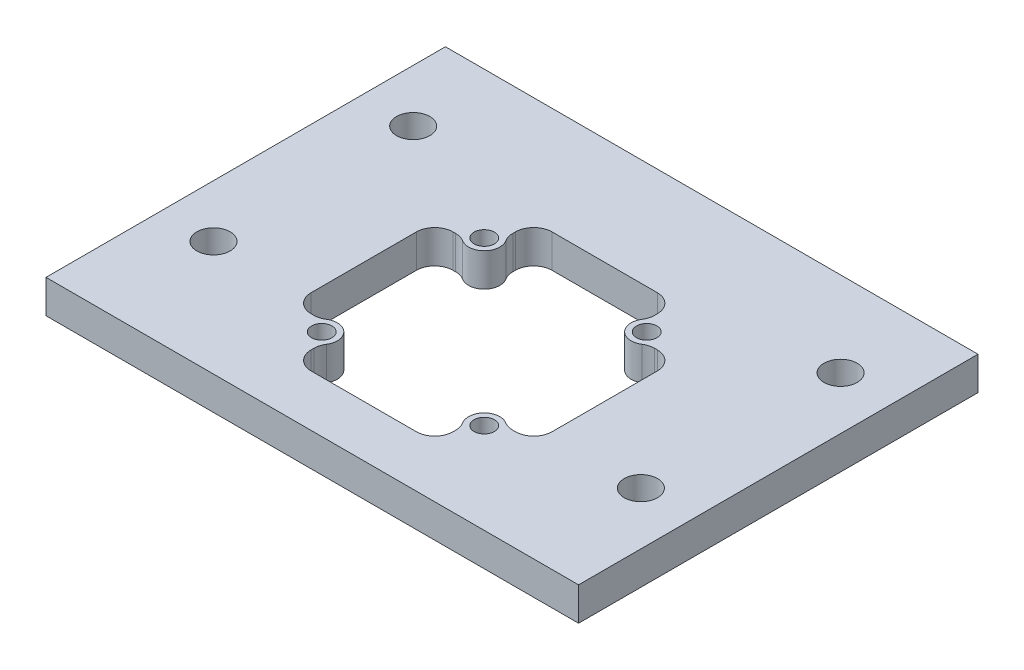
SolidWorks part; units mm, degrees
ref_plane "Front Plane" through (0, 0, 0) normal (0, 0, 1) x (1, 0, 0)
ref_plane "Top Plane" through (0, 0, 0) normal (0, 1, 0) x (1, 0, 0)
ref_plane "Right Plane" through (0, 0, 0) normal (1, 0, 0) x (0, 0, -1)
sketch "Sketch1" plane through (0, 0, 0) normal (0, 1, 0) x (1, 0, 0)
  line L1 (-50.8, 38.1) -> (50.8, 38.1)
  line L2 (-50.8, 38.1) -> (-50.8, -38.1)
  line L3 (-50.8, -38.1) -> (50.8, -38.1)
  line L4 (50.8, 38.1) -> (50.8, -38.1)
  line L5 (-50.8, 38.1) -> (50.8, -38.1) construction
  line L6 (-50.8, -38.1) -> (50.8, 38.1) construction
  point P0 (0, 0)
  dimension "D1" = 101.6
  dimension "D2" = 76.2
extrude "Boss-Extrude1" add sketch "Sketch1" along normal mid plane 6.35
sketch "Sketch16" plane through (0, 3.175, 0) normal (0, 1, 0) x (1, 0, 0)
  line L0 (50.8, 38.1) -> (-50.8, 38.1) construction
  line L1 (-50.8, 38.1) -> (-50.8, -38.1) construction
  line L2 (0, -55) -> (0, 55) construction
  point P0 (-30, 12.7)
  point P10 (30, 12.7)
  dimension "D1" = 25.4
  dimension "D2" = 20.8
sketch "Sketch25" plane through (0, 3.175, 0) normal (0, 1, 0) x (1, 0, 0)
  point P0 (-40.767, 21.9177)
  point P1 (-40.767, -16.1823)
  dimension "D1" = 40.767
  dimension "D2" = 38.1
hole_wizard "1/4 (0.25) Diameter Hole1" positions "Sketch26" profile "Sketch27" hole size "1/4" standard "ANSI Inch" end condition through all
sketch "Sketch26" plane through (0, 3.175, 0) normal (0, 1, 0) x (1, 0, 0)
  point P0 (-40.767, 21.9177)
  point P3 (-40.767, -16.1823)
sketch "Sketch27" plane through (-40.767, 3.175, -21.9177) normal (1, 0, 0) x (0, 0, 1)
  line L0 (0, 0) -> (0, 6.35)
  line L1 (0, 6.35) -> (3.175, 6.35)
  line L2 (3.175, 6.35) -> (3.175, 0)
  line L5 (3.175, 0) -> (0, 0)
  line L11 (0, -6.35) -> (0, 107.95) construction
  dimension "Thru Hole Dia." = 6.35
  dimension "Thru Hole Depth" = 6.35
sketch "Sketch17" plane through (0, 3.175, 0) normal (0, 1, 0) x (1, 0, 0)
  line L0 (-30, 12.7) -> (30, 12.7) construction
  line L1 (-21, -26.3) -> (21, -26.3) construction
  line L2 (-21, -26.3) -> (-21, 15.7) construction
  line L3 (-21, 15.7) -> (21, 15.7) construction
  line L4 (21, -26.3) -> (21, 15.7) construction
  line L5 (-21, -26.3) -> (21, 15.7) construction
  line L6 (-21, 15.7) -> (21, -26.3) construction
  line L7 (-15.5, -20.8) -> (15.5, -20.8) construction
  line L8 (-15.5, -20.8) -> (-15.5, 10.2) construction
  line L9 (-15.5, 10.2) -> (15.5, 10.2) construction
  line L10 (15.5, -20.8) -> (15.5, 10.2) construction
  line L11 (-15.5, -20.8) -> (15.5, 10.2) construction
  line L12 (-15.5, 10.2) -> (15.5, -20.8) construction
  point P0 (0, -5.3)
  point P5 (0, -5.3)
  point P10 (0, 12.7)
  dimension "D1" = 31
  dimension "D2" = 42
  dimension "D3" = 18
hole_wizard "M3.5 Clearance Hole1" positions "Sketch19" profile "Sketch20" hole size "M3.5" standard "ANSI Metric" end condition through all
sketch "Sketch19" plane through (0, 3.175, 0) normal (0, 1, 0) x (1, 0, 0)
  point P0 (-15.5, 10.2)
  point P3 (15.5, 10.2)
  point P6 (15.5, -20.8)
  point P9 (-15.5, -20.8)
sketch "Sketch20" plane through (-15.5, 3.175, -10.2) normal (1, 0, 0) x (0, 0, 1)
  line L0 (0, 0) -> (0, 6.35)
  line L1 (0, 6.35) -> (1.95, 6.35)
  line L2 (1.95, 6.35) -> (1.95, 0)
  line L5 (1.95, 0) -> (0, 0)
  line L11 (0, -6.35) -> (0, 107.95) construction
  dimension "Thru Hole Dia." = 3.9
  dimension "Thru Hole Depth" = 6.35
sketch "Sketch21" plane through (0, 3.175, 0) normal (0, 1, 0) x (1, 0, 0)
  line L0 (-12.9661, 15.7) -> (-12.9661, 11.806) construction
  line L1 (-12.9661, 15.7) -> (12.9661, 15.7) construction
  line L2 (-21, 7.6661) -> (-21, -18.2661) construction
  line L3 (-12.9661, -26.3) -> (12.9661, -26.3) construction
  line L4 (21, 7.6661) -> (21, -18.2661) construction
  line L5 (-15.5, 10.2) -> (15.5, -20.8) construction
  line L7 (12.9661, 15.7) -> (12.9661, 11.806) construction
  line L9 (-21, -18.2661) -> (-17.106, -18.2661) construction
  line L11 (12.9661, -26.3) -> (12.9661, -22.406) construction
  line L13 (-21, -26.3) -> (-21, 15.7) construction
  line L16 (-21, -26.3) -> (21, -26.3) construction
  line L18 (-21, 15.7) -> (21, 15.7) construction
  line L19 (21, -26.3) -> (21, 15.7) construction
  line L22 (-17.106, 7.6661) -> (-21, 7.6661) construction
  line L23 (-44.1452, 24.0875) -> (-44.1452, 20.9125) construction
  line L24 (17.106, 7.6661) -> (21, 7.6661) construction
  line L25 (17.106, -18.2661) -> (21, -18.2661) construction
  line L26 (-12.9661, -22.406) -> (-12.9661, -26.3) construction
  arc A0 (-17.106, 7.6661) -> (-12.9661, 11.806) centre (-15.5, 10.2) ccw construction
  arc A1 (12.9661, 11.806) -> (17.106, 7.6661) centre (15.5, 10.2) ccw construction
  arc A2 (17.106, -18.2661) -> (12.9661, -22.406) centre (15.5, -20.8) ccw construction
  arc A3 (-12.9661, -22.406) -> (-17.106, -18.2661) centre (-15.5, -20.8) ccw construction
  point P4 (0, -5.3)
  point P5 (-0.6681, -3.4714)
  point P13 (0, -5.3)
  point P15 (0, 0)
  dimension "D2" = 6
  dimension "D1" = 3.894
sketch "Sketch23" plane through (0, 3.175, 0) normal (0, 1, 0) x (1, 0, 0)
  line L0 (-12.9861, 15.72) -> (-12.9861, 11.8002)
  line L1 (-12.9861, 15.72) -> (12.9861, 15.72)
  line L2 (-21.02, 7.6861) -> (-21.02, -18.2861)
  line L3 (-12.9861, -26.32) -> (12.9861, -26.32)
  line L4 (21.02, 7.6861) -> (21.02, -18.2861)
  line L5 (12.9861, 15.72) -> (12.9861, 11.8002)
  line L6 (-21.02, -18.2861) -> (-17.1002, -18.2861)
  line L7 (12.9861, -26.32) -> (12.9861, -22.4002)
  line L8 (-17.1002, 7.6861) -> (-21.02, 7.6861)
  line L9 (17.1002, 7.6861) -> (21.02, 7.6861)
  line L10 (17.1002, -18.2861) -> (21.02, -18.2861)
  line L11 (-12.9861, -22.4002) -> (-12.9861, -26.32)
  line L16 (21, 7.6661) -> (21, -18.2661) construction
  line L19 (-12.9661, 15.7) -> (12.9661, 15.7) construction
  line L20 (12.9661, 15.7) -> (12.9661, 11.806) construction
  arc A0 (-17.1002, 7.6861) -> (-12.9861, 11.8002) centre (-15.5, 10.2) ccw
  arc A1 (12.9861, 11.8002) -> (17.1002, 7.6861) centre (15.5, 10.2) ccw
  arc A2 (17.1002, -18.2861) -> (12.9861, -22.4002) centre (15.5, -20.8) ccw
  arc A3 (-12.9861, -22.4002) -> (-17.1002, -18.2861) centre (-15.5, -20.8) ccw
  arc A4 (12.9661, 11.806) -> (17.106, 7.6661) centre (15.5, 10.2) ccw construction
  circle A5 centre (-15.5, 10.2) radius 1.95 construction
  dimension "D2" = 0.02
  dimension "D1" = 0.02
  dimension "D4" = 0.02
  dimension "D5" = 0.02
extrude "Cut-Extrude6" cut sketch "Sketch23" against normal through all
sketch "Sketch24" plane through (0, 3.175, 0) normal (0, 1, 0) x (1, 0, 0)
  line L0 (-18.9796, 8.2335) -> (-19.4796, 8.2335)
  line L1 (-22.9796, 4.7335) -> (-22.9796, -15.3335)
  line L2 (-19.4796, -18.8335) -> (-18.9796, -18.8335)
  line L4 (-15.5, 10.2) -> (15.5, -20.8) construction
  line L5 (-12.9861, 11.8002) -> (-7.9861, 11.8002)
  line L6 (-7.9861, 11.8002) -> (-7.9861, -22.4002)
  line L7 (-7.9861, -22.4002) -> (-12.9861, -22.4002)
  arc A0 (-17.1002, 7.6861) -> (-18.9796, 8.2335) centre (-18.9796, 4.7335) ccw
  arc A1 (-17.1002, 7.6861) -> (-12.9861, 11.8002) centre (-15.5, 10.2) ccw construction
  arc A3 (-19.4796, 8.2335) -> (-22.9796, 4.7335) centre (-19.4796, 4.7335) ccw
  arc A7 (-18.9796, -18.8335) -> (-17.1002, -18.2861) centre (-18.9796, -15.3335) ccw
  arc A8 (-22.9796, -15.3335) -> (-19.4796, -18.8335) centre (-19.4796, -15.3335) ccw
  arc A9 (-17.1002, 7.6861) -> (-12.9861, 11.8002) centre (-15.5, 10.2) ccw
  arc A10 (-12.9861, -22.4002) -> (-17.1002, -18.2861) centre (-15.5, -20.8) ccw construction
  arc A11 (-12.9861, -22.4002) -> (-17.1002, -18.2861) centre (-15.5, -20.8) ccw
  point P9 (0, -5.3)
  dimension "D3" = 5
  dimension "D4" = 3.5
  dimension "D5" = 0.5
extrude "Cut-Extrude7" cut sketch "Sketch24" against normal through all
ref_axis "Axis1" through (0, 3.175, 5.3) along (0, 1, 0)
pattern_circular "CirPattern1" count 4 over 360 about axis through (0, 3.175, 5.3) along (0, 1, 0) of "Cut-Extrude7"
mirror "Mirror2" about plane through (0, 0, 0) normal (1, 0, 0) of "1/4 (0.25) Diameter Hole1"
